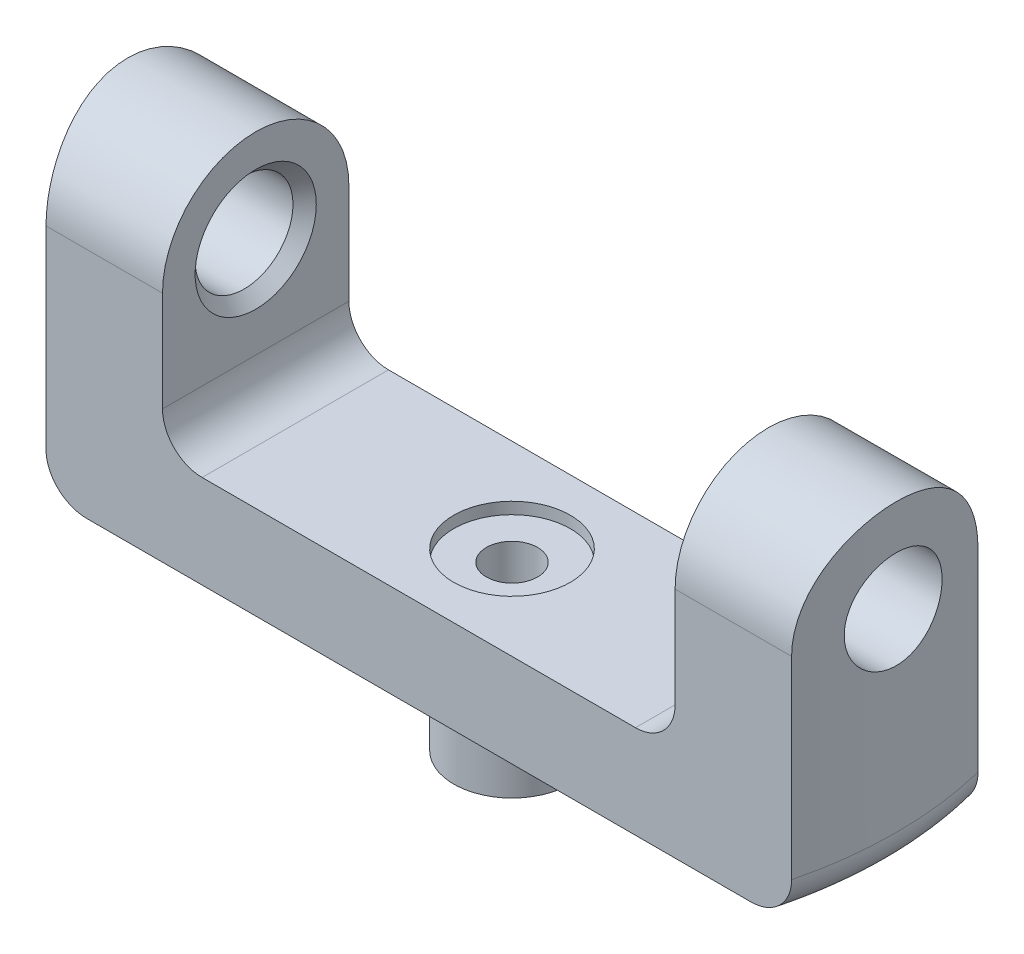
SolidWorks part; units mm, degrees
ref_plane "Front Plane" through (0, 0, 0) normal (0, 0, 1) x (1, 0, 0)
ref_plane "Top Plane" through (0, 0, 0) normal (0, 1, 0) x (1, 0, 0)
ref_plane "Right Plane" through (0, 0, 0) normal (1, 0, 0) x (0, 0, -1)
sketch "Sketch1" plane through (0, 0, 0) normal (0, 1, 0) x (1, 0, 0)
  line L1 (16, 4) -> (-16, 4)
  line L2 (16, 4) -> (16, -4)
  line L3 (16, -4) -> (-16, -4)
  line L4 (-16, 4) -> (-16, -4)
  line L5 (11, -4) -> (-11, -4)
  line L6 (11, -4) -> (11, 4)
  line L7 (11, 4) -> (-11, 4)
  line L8 (-11, -4) -> (-11, 4)
  line L9 (0, 4) -> (0, -4) construction
  line L10 (11, 0) -> (-11, 0) construction
  circle A0 centre (0, 0) radius 16.4924
  dimension "D1" = 5
  dimension "D2" = 8
  dimension "D3" = 22
extrude "Boss-Extrude1" add sketch "Sketch1" along normal blind 4 contours L3 L8 L1 L4 | L8 L3 L6 L1 | L6 L3 L2 L1 | L4 A0 | L2 A0 region at (13.5, 0, 0) region at (16.1972, 0, 0) region at (0, 0, 0) region at (-13.5, 0, 0) region at (-16.1972, 0, 0)
extrude "Boss-Extrude2" add sketch "Sketch1<3>" along normal blind 10 from surface contours L3 L8 L1 L4 | L4 A0 | L6 L3 L2 L1 | L2 A0 region at (13.5, 0, 0) region at (16.1972, 0, 0) region at (-13.5, 0, 0) region at (-16.1972, 0, 0) starting at face at (0, 4, 0)
sketch "Sketch1<3>" plane through (0, 0, 0) normal (0, 1, 0) x (1, 0, 0) same geometry as "Sketch1"
sketch "Sketch2" plane through (-11, 0, 0) normal (1, 0, 0) x (0, 0, -1)
  line L2 (4, 14) -> (-4, 14) construction
  line L4 (-4, 14) -> (-4, 4) construction
  line L5 (4, 14) -> (4, 4) construction
  circle A0 centre (0, 10) radius 2.1
  arc A1 (-4, 10) -> (4, 10) centre (0, 10) cw
  line M2 (4, 4) -> (4, 14)
  line M3 (4, 14) -> (-4, 14)
  line M4 (-4, 14) -> (-4, 4)
  dimension "D1" = 4.2
extrude "Cut-Extrude1" cut sketch "Sketch2" against normal through all both and the other way through all contours A1 M3 M2 | A1 M4 M3 | A0 region at (-11, 10, 0) region at (-11, 13.1065, 3.1065) region at (-11, 13.1065, -3.1065)
sketch "Sketch4" plane through (0, 0, 0) normal (0, -1, 0) x (1, 0, 0)
  circle A0 centre (0, 0) radius 2.5
  dimension "D1" = 5
extrude "Boss-Extrude3" add sketch "Sketch4" along normal blind 3.5
sketch "Sketch5" plane through (0, -3.5, 0) normal (0, -1, 0) x (1, 0, 0)
  circle A0 centre (0, 0) radius 1.1
  dimension "D1" = 2.2
extrude "Cut-Extrude2" cut sketch "Sketch5" against normal through all both and the other way through all
sketch "Sketch6" plane through (0, 4, 0) normal (0, 1, 0) x (1, 0, 0)
  circle A0 centre (0, 0) radius 2.5
  dimension "D1" = 5
extrude "Cut-Extrude3" cut sketch "Sketch6" against normal blind 0.5
chamfer "Chamfer1" distance 0.5 angle 45 2 edges at (11, 10, -2.1) (-11, 10, -2.1)
fillet "Fillet1" radius 1.7 4 edges at (16.4924, 0, 0) (-16.4924, 0, 0) (-11, 4, 0) (11, 4, 0)
equation "\"bandwidth\"= 20mm"
equation "\"loosefit\"= 0.5mm"
equation "\"tightfit\"= 0.2mm"
equation "\"D3@Sketch1\"=\"bandwidth\" + 4*\"loosefit\""
